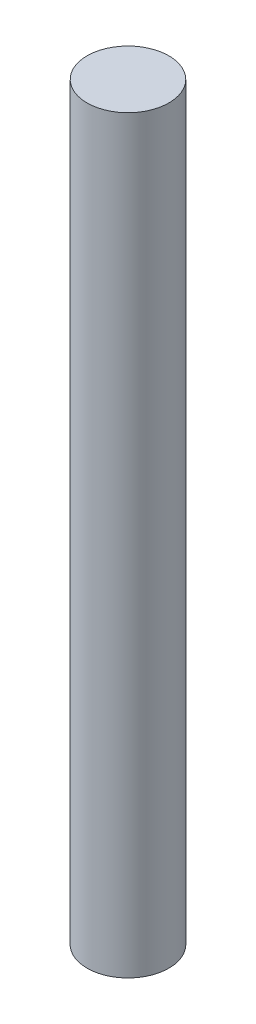
SolidWorks part; units mm, degrees
material "AISI 1020"
ref_plane "Front Plane" through (0, 0, 0) normal (0, 0, 1) x (1, 0, 0)
ref_plane "Top Plane" through (0, 0, 0) normal (0, 1, 0) x (1, 0, 0)
ref_plane "Right Plane" through (0, 0, 0) normal (1, 0, 0) x (0, 0, -1)
sketch "Sketch2" plane through (0, 0, 0) normal (0, 1, 0) x (1, 0, 0)
  circle A0 centre (0, 0) radius 3
  dimension "D1" = 6
extrude "Boss-Extrude1" add sketch "Sketch2" along normal blind 55
